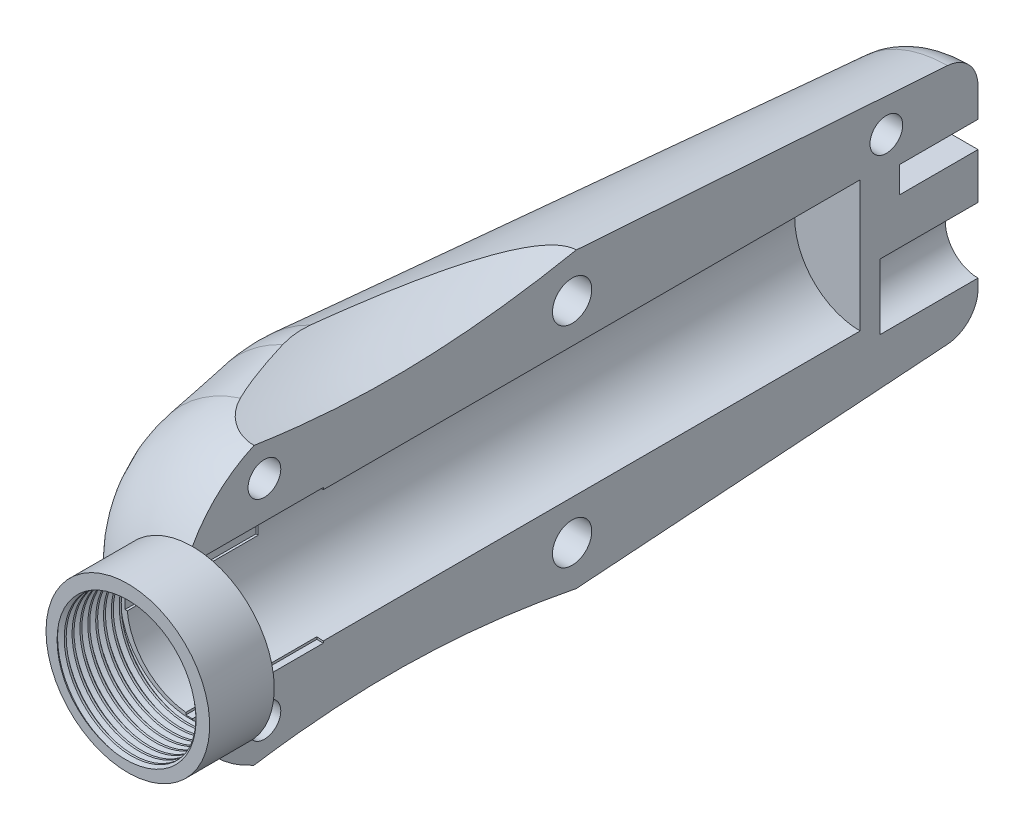
SolidWorks part; units mm, degrees
ref_plane "Ön Düzlem" through (0, 0, 0) normal (0, 0, 1) x (1, 0, 0)
ref_plane "Üst Düzlem" through (0, 0, 0) normal (0, 1, 0) x (1, 0, 0)
ref_plane "Sağ Düzlem" through (0, 0, 0) normal (1, 0, 0) x (0, 0, -1)
sketch "Sketch1" plane through (0, 0, 0) normal (0, 0, 1) x (1, 0, 0)
  circle A0 centre (0, 0) radius 5
  circle A1 centre (0, 0) radius 11.25
  dimension "D1" = 10
  dimension "D2" = 22.5
extrude "Boss-Extrude1" add sketch "Sketch1" along normal blind 51
sketch "Sketch2" plane through (0, 0, 0) normal (0, 0, -1) x (-1, 0, 0)
  circle A0 centre (0, 0) radius 11.25
extrude "Boss-Extrude2" add sketch "Sketch2" along normal blind 9
sketch "Sketch3" plane through (0, 0, -9) normal (0, 0, -1) x (-1, 0, 0)
  line L0 (-2, 4.5) -> (-3, 3.5)
  line L1 (-3, 2.5) -> (3, 2.5)
  line L2 (-3, 2.5) -> (-3, 3.5)
  line L3 (-2, 4.5) -> (2, 4.5)
  line L4 (3, 2.5) -> (3, 3.5)
  line L5 (3, 3.5) -> (2, 4.5)
  point P4 (0, 2.5)
  dimension "D1" = 6
  dimension "D3" = 2.5
  dimension "D4" = 4
  dimension "D5" = 45
extrude "Cut-Extrude1" cut sketch "Sketch3" against normal blind 6
sketch "Sketch4" plane through (0, 0, -9) normal (0, 0, -1) x (-1, 0, 0)
  line L1 (-5, -1) -> (5, -1)
  line L2 (-5, -1) -> (-5, -3.5)
  line L3 (-5, -3.5) -> (5, -3.5)
  line L4 (5, -1) -> (5, -3.5)
  point P4 (0, -3.5)
  dimension "D1" = 10
  dimension "D2" = 2.5
  dimension "D3" = 1
extrude "Cut-Extrude2" cut sketch "Sketch4" against normal blind 5 from offset 2.5 offset against normal yes
sketch "Sketch5" plane through (0, 0, -9) normal (0, 0, -1) x (-1, 0, 0)
  circle A0 centre (0, -3.5) radius 2.5
  dimension "D1" = 5
  dimension "D2" = 3.5
extrude "Cut-Extrude3" cut sketch "Sketch5" against normal blind 7.5
sketch "Sketch6" plane through (0, 0, 51) normal (0, 0, 1) x (1, 0, 0)
  line L0 (0.5, 4.9) -> (-0.5, 4.9)
  line L1 (-4.9, 0.5) -> (-5.15, 0.5)
  line L2 (-4.9, 0.5) -> (-4.9, -0.5)
  line L3 (-4.9, -0.5) -> (-5.15, -0.5)
  line L4 (-5.15, 0.5) -> (-5.15, -0.5)
  line L5 (0.5, 4.9) -> (0.5, 5.15)
  line L6 (0.5, 5.15) -> (-0.5, 5.15)
  line L7 (-0.5, 4.9) -> (-0.5, 5.15)
  line L8 (4.9, -0.5) -> (4.9, 0.5)
  line L9 (4.9, -0.5) -> (5.15, -0.5)
  line L10 (5.15, -0.5) -> (5.15, 0.5)
  line L11 (4.9, 0.5) -> (5.15, 0.5)
  line L12 (-0.5, -4.9) -> (0.5, -4.9)
  line L13 (-0.5, -4.9) -> (-0.5, -5.15)
  line L14 (-0.5, -5.15) -> (0.5, -5.15)
  line L15 (0.5, -4.9) -> (0.5, -5.15)
  point P4 (-4.9, 0)
  point P21 (0, 0)
  dimension "D1" = 1
  dimension "D2" = 0.25
  dimension "D3" = 4.9
  dimension "D4" = 4
extrude "Cut-Extrude4" cut sketch "Sketch6" against normal blind 10
sketch "Sketch7" plane through (0, 0, 51) normal (0, 0, 1) x (1, 0, 0)
  line L0 (-11.25, 11.25) -> (11.25, -11.25) construction
  line L1 (-11.25, 11.25) -> (11.25, 11.25)
  line L2 (-11.25, 11.25) -> (-11.25, -11.25)
  line L3 (-11.25, -11.25) -> (11.25, -11.25)
  line L4 (11.25, 11.25) -> (11.25, -11.25)
  circle A0 centre (0, 0) radius 7.5
  point P4 (0, 0)
  dimension "D3" = 15
  dimension "D1" = 22.5
  dimension "D2" = 22.5
extrude "Boss-Extrude3" add sketch "Sketch7" against normal blind 55
sketch "Sketch11" plane through (0, 0, 51) normal (0, 0, 1) x (1, 0, 0)
  circle A0 centre (0, 0) radius 5.5
  circle A1 centre (0, 0) radius 6.25
  dimension "D1" = 12.5
  dimension "D2" = 11
extrude "Boss-Extrude4" add sketch "Sketch11" along normal blind 5
thread "Thread1" pitch 0.6 method extrude profile "Thread Profile1" start angle 0, offset 1, length 6, pitch 0.6, diameter 11
ref_plane "Plane1" through (-5.5, 0, 57) normal (0, -1, 0) x (-1, 0, 0)
sketch "Thread Profile1" plane through (-5.5, 0, 57) normal (0, -1, 0) x (-1, 0, 0)
  line L0 (0, 0) -> (0, 0.6) construction
  line L11 (0, 0) -> (0, 0.525)
  line L12 (0, 0.525) -> (-0.3248, 0.3375)
  line L13 (-0.3248, 0.3375) -> (-0.3248, 0.1875)
  line L15 (-0.3248, 0.1875) -> (0, 0)
  line L17 (-0.3248, 0.2625) -> (0, 0.2625) construction
  point P2 (0, 0)
  dimension "Pitch" = 0.6
  dimension "Profile_Angle" = 60
  dimension "Profile_Land" = 0.15
  dimension "Profile_Height" = 0.3248
sketch "Sketch14" plane through (11.25, 0, 0) normal (1, 0, 0) x (0, 0, -1)
  line L1 (-70.4093, 18.7396) -> (-55.9318, 18.7396)
  line L2 (-70.4093, 18.7396) -> (-70.4093, -13.801)
  line L3 (-70.4093, -13.801) -> (-55.9318, -13.801)
  line L4 (-55.9318, 18.7396) -> (-55.9318, -13.801)
extrude "Cut-Extrude5" cut sketch "Sketch14" against normal blind 30
sketch "Sketch15" plane through (0, 0, 0) normal (0, 1, 0) x (1, 0, 0)
  line L0 (-9, 9.75) -> (-12.3215, -37.75)
  line L1 (-12.3215, -37.75) -> (-9, -57.75)
  line L2 (11.25, 9) -> (-11.25, 9) construction
  line L3 (-9, 9.75) -> (-54, 9.75)
  line L4 (-54, 9.75) -> (-54, -633.78)
  line L5 (0, 0) -> (0, 16.5551) construction
  line L6 (-9, -57.75) -> (-13.7201, -57.75)
  line L7 (-13.7201, -57.75) -> (-54, -633.78)
  dimension "D1" = 9
  dimension "D2" = 0.75
  dimension "D3" = 45
  dimension "D4" = 86
  dimension "D5" = 47.5
  dimension "D6" = 67.5
revolve "Cut-Revolve2" cut sketch "Sketch15" angle 360 about L5
ref_plane "Plane2" through (0, 22.25, 0) normal (0, 1, 0) x (1, 0, 0)
sketch "Sketch17" plane through (0, 22.25, 0) normal (0, 1, 0) x (1, 0, 0)
  line L0 (0, 0) -> (0, -1000) construction
  line L1 (0, 8.75) -> (-7.5, -8.75) construction
  line L2 (-7.5, -8.75) -> (7.5, -8.75) construction
  line L3 (7.5, -8.75) -> (-12.5, -35.75) construction
  line L4 (-12.5, -35.75) -> (12.5, -35.75) construction
  line L5 (12.5, -35.75) -> (-7.5, -62.75) construction
  line L6 (-7.5, -62.75) -> (7.5, -62.75) construction
  line L7 (7.5, -62.75) -> (0, -80.25) construction
  line L8 (0, 8.75) -> (0, -80.25)
  spline S0 degree 3 poles (0, 8.75) (-6.8374, -4.8333) (-18.1626, -35.75) (-6.8374, -66.6667) (0, -80.25) knots 0 0 0 0 0.5 1 1 1 1
  point P5 (0, -8.75)
  point P12 (0, -35.75)
  point P13 (0, -62.75)
  dimension "D1" = 1000
  dimension "D2" = 17.5
  dimension "D3" = 17.5
  dimension "D4" = 27
  dimension "D5" = 27
  dimension "D6" = 15
  dimension "D7" = 25
  dimension "D8" = 15
  dimension "D9" = 8.75
revolve "Cut-Revolve3" cut sketch "Sketch17" angle 360 about L8
pattern_circular "CirPattern1" count 4 over 360 about axis through (0, 0, 56) along (0, 0, -1) of "Cut-Revolve3"
fillet "Fillet1" radius 10 1 edges at (10.121, 0, 51)
fillet "Fillet2" radius 10 4 edges at (-8.7126, 8.7126, 37.75) (-8.7126, -8.7126, 37.75) (8.7126, -8.7126, 37.75) (8.7126, 8.7126, 37.75)
fillet "Fillet5" radius 2.5 1 edges at (-9.0524, 0, -9)
sketch "Sketch19" plane through (0, 0, -9) normal (0, 0, -1) x (-1, 0, 0)
  line L1 (-15.617, 14.5318) -> (0, 14.5318)
  line L2 (-15.617, 14.5318) -> (-15.617, -15.9)
  line L3 (-15.617, -15.9) -> (0, -15.9)
  line L4 (0, 14.5318) -> (0, -15.9)
extrude "Cut-Extrude6" cut sketch "Sketch19" against normal blind 60
sketch "Sketch20" plane through (0, 0, 0) normal (1, 0, 0) x (0, 0, -1)
  line L0 (0, 0) -> (-19.9695, 0) construction
  circle A0 centre (-45.5, 8) radius 1.25
  circle A1 centre (-22, 8) radius 1.5
  circle A2 centre (2, 7) radius 1.25
  circle A3 centre (-22, -8) radius 1.5
  circle A4 centre (-45.5, -8) radius 1.25
  dimension "D1" = 3
  dimension "D2" = 2.5
  dimension "D3" = 2.5
  dimension "D4" = 22
  dimension "D5" = 2
  dimension "D6" = 7
  dimension "D7" = 8
  dimension "D8" = 23.5
extrude "Cut-Extrude7" cut sketch "Sketch20" against normal blind 3
